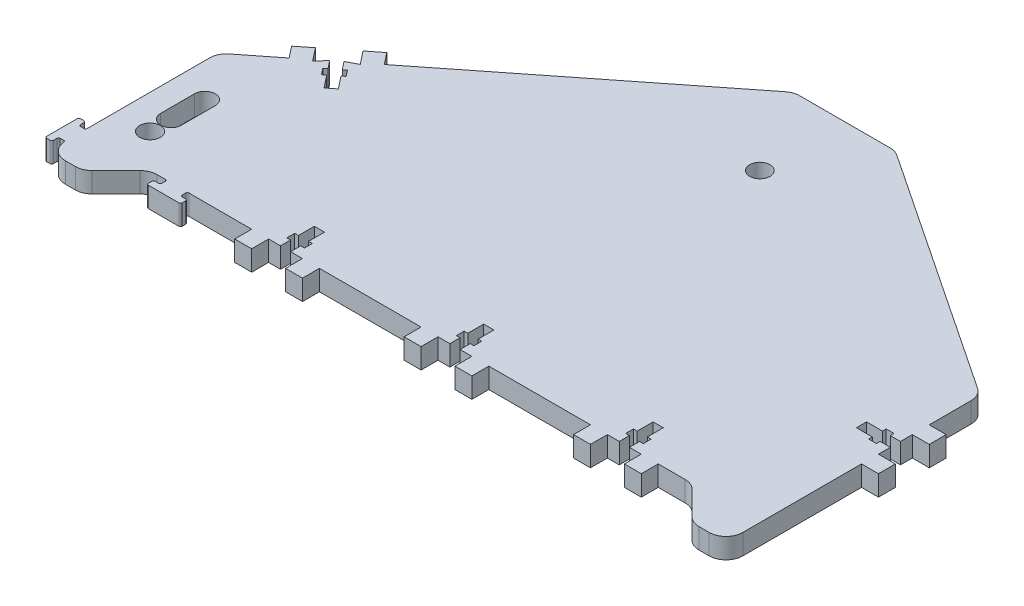
SolidWorks part; units mm, degrees
ref_plane "Front Plane" through (0, 0, 0) normal (0, 0, 1) x (1, 0, 0)
ref_plane "Top Plane" through (0, 0, 0) normal (0, 1, 0) x (1, 0, 0)
ref_plane "Right Plane" through (0, 0, 0) normal (1, 0, 0) x (0, 0, -1)
sketch "Sketch1" plane through (0, 0, 0) normal (0, 1, 0) x (1, 0, 0)
  line L0 (0, 0) -> (0, 131.8065) construction
  line L1 (45.2903, 100) -> (-54.9677, 100) construction
  line L2 (-100, 0) -> (-100, 59.0323) construction
  line L3 (-100, 0) -> (0, 0) construction
  line L4 (-121.1613, 41.6129) -> (-90.5806, 41.6129) construction
  line L5 (-85.6774, 20) -> (-114, 20) construction
  line L6 (-15, 125) -> (15, 125)
  line L7 (15, 125) -> (90, 75)
  line L8 (90, 75) -> (90, 0) construction
  line L9 (90, 0) -> (-110, 0) construction
  line L10 (-110, 0) -> (-110, 50) construction
  line L11 (-110, 50) -> (-15, 125) construction
  line L12 (-100, 26.2) -> (-100, 36.2) construction
  line L13 (-103.05, 26.2) -> (-103.05, 36.2)
  line L14 (-96.95, 26.2) -> (-96.95, 36.2)
  line L15 (-110, 0) -> (-100, 0)
  line L16 (-100, 0) -> (-90, 10)
  line L17 (-90, 10) -> (70, 10) construction
  line L18 (70, 10) -> (80, 0)
  line L19 (80, 0) -> (90, 0)
  line L20 (-90, 10) -> (-60, 10) construction
  line L21 (-40, 10) -> (-10, 10)
  line L22 (10, 10) -> (40, 10)
  line L23 (60, 10) -> (70, 10)
  line L24 (90, 40) -> (90, 0)
  line L25 (90, 60) -> (90, 75)
  line L26 (-98.2268, 59.2947) -> (-110, 50)
  line L27 (-82.5291, 71.6876) -> (-15, 125)
  line L28 (0, 10) -> (0, 21.2208) construction
  line L29 (-1.5, 10) -> (-5, 10)
  line L30 (-5, 5) -> (-10, 5)
  line L31 (-10, 5) -> (-10, 10)
  line L32 (-5, 5) -> (-5, 10)
  line L33 (1.5, 10) -> (5, 10)
  line L34 (5, 10) -> (5, 5)
  line L35 (5, 5) -> (10, 5)
  line L36 (10, 5) -> (10, 10)
  line L37 (90, 50) -> (78.7792, 50) construction
  line L38 (90, 48.5) -> (90, 45)
  line L39 (95, 45) -> (95, 40)
  line L40 (95, 40) -> (90, 40)
  line L41 (95, 45) -> (90, 45)
  line L42 (90, 51.5) -> (90, 55)
  line L43 (90, 55) -> (95, 55)
  line L44 (95, 55) -> (95, 60)
  line L45 (95, 60) -> (90, 60)
  line L46 (-90.44, 65.5698) -> (-85.3799, 59.1603) construction
  line L47 (-89.2627, 66.4992) -> (-86.1092, 68.1532)
  line L48 (-89.1391, 71.991) -> (-85.2147, 75.0893)
  line L49 (-85.2147, 75.0893) -> (-82.5291, 71.6876)
  line L50 (-89.1391, 71.991) -> (-86.1092, 68.1532)
  line L51 (-91.6174, 64.6403) -> (-93.958, 61.9567)
  line L52 (-93.958, 61.9567) -> (-96.9879, 65.7946)
  line L53 (-96.9879, 65.7946) -> (-100.9123, 62.6964)
  line L54 (-100.9123, 62.6964) -> (-98.2268, 59.2947)
  line L55 (-50, 10) -> (-50, 21.2208) construction
  line L56 (-51.5, 10) -> (-55, 10)
  line L57 (-55, 5) -> (-60, 5)
  line L58 (-60, 5) -> (-60, 10)
  line L59 (-55, 5) -> (-55, 10)
  line L60 (-48.5, 10) -> (-45, 10)
  line L61 (-45, 10) -> (-45, 5)
  line L62 (-45, 5) -> (-40, 5)
  line L63 (-40, 5) -> (-40, 10)
  line L64 (50, 10) -> (50, 21.2208) construction
  line L65 (48.5, 10) -> (45, 10)
  line L66 (45, 5) -> (40, 5)
  line L67 (40, 5) -> (40, 10)
  line L68 (45, 5) -> (45, 10)
  line L69 (51.5, 10) -> (55, 10)
  line L70 (55, 10) -> (55, 5)
  line L71 (55, 5) -> (60, 5)
  line L72 (60, 5) -> (60, 10)
  line L73 (-1.5, 10) -> (1.5, 10) construction
  line L74 (1.5, 10) -> (1.5, 13)
  line L75 (1.5, 15.3) -> (2.6, 15.3)
  line L76 (-2.6, 13) -> (-2.6, 15.3)
  line L77 (2.6, 13) -> (1.5, 13)
  line L78 (1.5, 15.3) -> (1.5, 20)
  line L79 (1.5, 20) -> (-1.5, 20)
  line L80 (-1.5, 20) -> (-1.5, 15.3)
  line L81 (-1.5, 13) -> (-2.6, 13)
  line L82 (2.6, 15.3) -> (2.6, 13)
  line L83 (-2.6, 15.3) -> (-1.5, 15.3)
  line L84 (-1.5, 13) -> (-1.5, 10)
  line L85 (0, 20) -> (0, 10) construction
  line L86 (90, 48.5) -> (90, 51.5) construction
  line L87 (90, 51.5) -> (87, 51.5)
  line L88 (84.7, 51.5) -> (84.7, 52.6)
  line L89 (87, 47.4) -> (84.7, 47.4)
  line L90 (87, 52.6) -> (87, 51.5)
  line L91 (84.7, 51.5) -> (80, 51.5)
  line L92 (80, 51.5) -> (80, 48.5)
  line L93 (80, 48.5) -> (84.7, 48.5)
  line L94 (87, 48.5) -> (87, 47.4)
  line L95 (84.7, 52.6) -> (87, 52.6)
  line L96 (84.7, 47.4) -> (84.7, 48.5)
  line L97 (87, 48.5) -> (90, 48.5)
  line L98 (80, 50) -> (90, 50) construction
  line L99 (-89.2627, 66.4992) -> (-91.6174, 64.6403) construction
  line L100 (-91.6174, 64.6403) -> (-89.7584, 62.2857)
  line L101 (-88.3332, 60.4804) -> (-89.1966, 59.7988)
  line L102 (-86.5404, 64.8262) -> (-85.1152, 63.021)
  line L103 (-90.6218, 61.604) -> (-89.7584, 62.2857)
  line L104 (-88.3332, 60.4804) -> (-85.4209, 56.7915)
  line L105 (-85.4209, 56.7915) -> (-83.0663, 58.6504)
  line L106 (-83.0663, 58.6504) -> (-85.9786, 62.3394)
  line L107 (-87.4038, 64.1446) -> (-86.5404, 64.8262)
  line L108 (-89.1966, 59.7988) -> (-90.6218, 61.604)
  line L109 (-85.1152, 63.021) -> (-85.9786, 62.3394)
  line L110 (-87.4038, 64.1446) -> (-89.2627, 66.4992)
  line L111 (-84.2436, 57.7209) -> (-90.44, 65.5698) construction
  line L112 (-51.5, 10) -> (-48.5, 10) construction
  line L113 (-48.5, 10) -> (-48.5, 13)
  line L114 (-48.5, 15.3) -> (-47.4, 15.3)
  line L115 (-52.6, 13) -> (-52.6, 15.3)
  line L116 (-47.4, 13) -> (-48.5, 13)
  line L117 (-48.5, 15.3) -> (-48.5, 20)
  line L118 (-48.5, 20) -> (-51.5, 20)
  line L119 (-51.5, 20) -> (-51.5, 15.3)
  line L120 (-51.5, 13) -> (-52.6, 13)
  line L121 (-47.4, 15.3) -> (-47.4, 13)
  line L122 (-52.6, 15.3) -> (-51.5, 15.3)
  line L123 (-51.5, 13) -> (-51.5, 10)
  line L124 (-50, 20) -> (-50, 10) construction
  line L125 (48.5, 10) -> (51.5, 10) construction
  line L126 (51.5, 10) -> (51.5, 13)
  line L127 (51.5, 15.3) -> (52.6, 15.3)
  line L128 (47.4, 13) -> (47.4, 15.3)
  line L129 (52.6, 13) -> (51.5, 13)
  line L130 (51.5, 15.3) -> (51.5, 20)
  line L131 (51.5, 20) -> (48.5, 20)
  line L132 (48.5, 20) -> (48.5, 15.3)
  line L133 (48.5, 13) -> (47.4, 13)
  line L134 (52.6, 15.3) -> (52.6, 13)
  line L135 (47.4, 15.3) -> (48.5, 15.3)
  line L136 (48.5, 13) -> (48.5, 10)
  line L137 (50, 20) -> (50, 10) construction
  line L138 (-110, 0) -> (-110, 5)
  line L139 (-110, 5) -> (-112, 5)
  line L140 (-112, 5) -> (-112, 3)
  line L141 (-112, 3) -> (-114, 3)
  line L142 (-114, 3) -> (-114, 13)
  line L143 (-114, 13) -> (-112, 13)
  line L144 (-112, 13) -> (-112, 11)
  line L145 (-112, 11) -> (-110, 11)
  line L146 (-110, 11) -> (-110, 50)
  line L147 (-90, 10) -> (-85, 10)
  line L148 (-85, 10) -> (-85, 8)
  line L149 (-85, 8) -> (-87, 8)
  line L150 (-87, 8) -> (-87, 6)
  line L151 (-87, 6) -> (-77, 6)
  line L152 (-77, 6) -> (-77, 8)
  line L153 (-77, 8) -> (-79, 8)
  line L154 (-79, 8) -> (-79, 10)
  line L155 (-79, 10) -> (-60, 10)
  line L156 (-114, 8) -> (-110, 8) construction
  line L157 (-82, 6) -> (-82, 10) construction
  circle A0 centre (0, 100) radius 82.5 construction
  circle A1 centre (0, 100) radius 10 construction
  circle A2 centre (0, 100) radius 3
  circle A3 centre (-100, 20) radius 3.05
  arc A4 (-103.05, 26.2) -> (-96.95, 26.2) centre (-100, 26.2) ccw
  arc A5 (-96.95, 36.2) -> (-103.05, 36.2) centre (-100, 36.2) ccw
  point P25 (-100, 31.2)
  point P173 (15, 107.6171)
  dimension "D2" = 165
  dimension "D3" = 20
  dimension "D4" = 6
  dimension "D5" = 6.1
  dimension "D6" = 3.05
  dimension "D1" = 100
  dimension "D7" = 6.2
  dimension "D8" = 10
  dimension "D9" = 100
  dimension "D10" = 30
  dimension "D11" = 25
  dimension "D12" = 90
  dimension "D13" = 50
  dimension "D14" = 50
  dimension "D15" = 10
  dimension "D16" = 10
  dimension "D17" = 10
  dimension "D18" = 10
  dimension "D19" = 10
  dimension "D20" = 20
  dimension "D21" = 50
  dimension "D22" = 50
  dimension "D23" = 25
  dimension "D24" = 50
  dimension "D25" = 10
  dimension "D26" = 5
  dimension "D27" = 2
  dimension "D28" = 10
  dimension "D29" = 5
  dimension "D30" = 2
  dimension "D31" = 10
  dimension "D32" = 5
  dimension "D33" = 8
  dimension "D34" = 10
  dimension "D35" = 5
  dimension "D36" = 8
  dimension "D37" = 10
  dimension "D38" = 5
  dimension "D39" = 6
  dimension "D40" = 5.2
  dimension "D41" = 3
  dimension "D42" = 2.3
  dimension "D43" = 3
  dimension "D44" = 10
  dimension "D45" = 5.2
  dimension "D46" = 3
  dimension "D47" = 2.3
  dimension "D48" = 3
  dimension "D49" = 10
  dimension "D50" = 5.2
  dimension "D51" = 3
  dimension "D52" = 2.3
  dimension "D53" = 3
  dimension "D54" = 10
  dimension "D55" = 5.2
  dimension "D56" = 3
  dimension "D57" = 2.3
  dimension "D58" = 3
  dimension "D59" = 10
  dimension "D60" = 5.2
  dimension "D61" = 3
  dimension "D62" = 2.3
  dimension "D63" = 3
  dimension "D64" = 10
  dimension "D65" = 6
extrude "Boss-Extrude1" add sketch "Sketch1" along normal blind 6
fillet "Fillet2" radius 5 10 edges at (90, 3, -75) (70, 3, -10) (90, 3, 0) (80, 3, 0) (-100, 3, 0) (-15, 3, -125) (15, 3, -125) (-110, 3, -50) (-90, 3, -10) (-110, 3, 0)
fillet "Fillet3" radius 0.5 16 edges at (-114, 3, -3) (-114, 3, -13) (-112, 3, -13) (-112, 3, -11) (-110, 3, -11) (-110, 3, -5) (-112, 3, -5) (-112, 3, -3) (-77, 3, -6) (-87, 3, -6) (-87, 3, -8) (-85, 3, -8) (-85, 3, -10) (-79, 3, -10) (-77, 3, -8) (-79, 3, -8)
